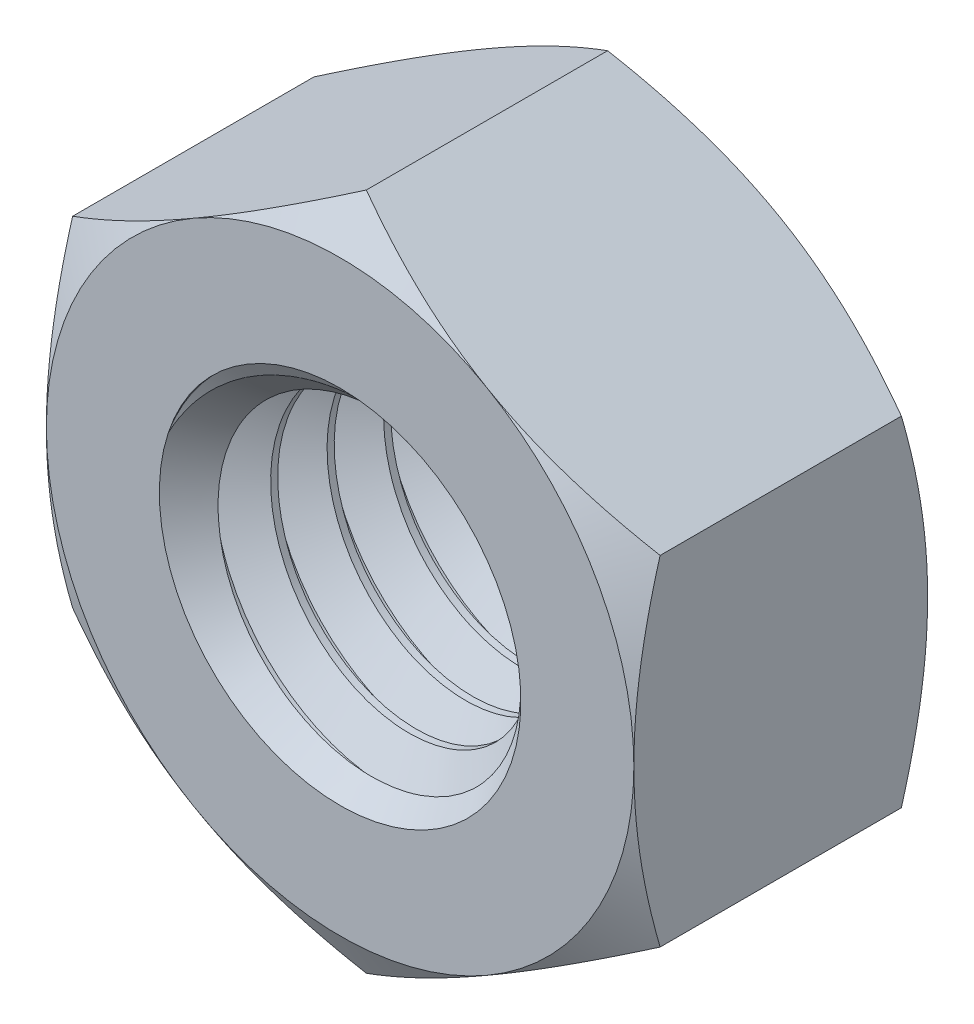
SolidWorks part; units mm, degrees
ref_plane "Front" through (0, 0, 0) normal (0, 0, 1) x (1, 0, 0)
ref_plane "Top" through (0, 0, 0) normal (0, 1, 0) x (1, 0, 0)
ref_plane "Right" through (0, 0, 0) normal (1, 0, 0) x (0, 0, -1)
sketch "Sketch1" plane through (0, 0, 0) normal (0, 0, 1) x (1, 0, 0)
  line L1 (-6.5, 3.7528) -> (-6.5, -3.7528)
  line L2 (-6.5, -3.7528) -> (0, -7.5056)
  line L3 (0, -7.5056) -> (6.5, -3.7528)
  line L4 (6.5, -3.7528) -> (6.5, 3.7528)
  line L5 (6.5, 3.7528) -> (0, 7.5056)
  line L6 (0, 7.5056) -> (-6.5, 3.7528)
  circle A0 centre (0, 0) radius 6.5 construction
  circle A1 centre (0, 0) radius 4 construction
  point P10 (0, 4)
  dimension "hex" = 13
  dimension "dia" = 8
extrude "Extrude1" add sketch "Sketch1" along normal mid plane 6.5
sketch "Sketch4" plane through (0, 0, -3.25) normal (0, 0, -1) x (-1, 0, 0)
  circle A0 centre (0, 0) radius 4 construction
  circle A1 centre (0, 0) radius 4
sketch "Sketch10" plane through (0, 0, 3.25) normal (0, 0, 1) x (1, 0, 0)
  circle A0 centre (0, 0) radius 4 construction
  circle A1 centre (0, 0) radius 4
extrude "Cut-Extrude2" cut sketch "Sketch10" against normal through all draft 45
sketch "Sketch11" plane through (0, 0, -3.25) normal (0, 0, -1) x (-1, 0, 0)
  circle A0 centre (0, 0) radius 4 construction
  circle A1 centre (0, 0) radius 4
extrude "Cut-Extrude3" cut sketch "Sketch11" against normal through all draft 45
sketch "Sketch13" plane through (0, 0, -3.25) normal (0, 0, -1) x (-1, 0, 0)
  circle A0 centre (0, 0) radius 4 construction
  circle A1 centre (0, 0) radius 4
extrude "Boss-Extrude1" add sketch "Sketch13" against normal up to vertex (6.5 mm away) separate body up to point (-6.5, 3.7528, 3.25)
curve "Helix/Spiral3" pitch 1.25 height 6.5 turns 5.2
sketch "Sketch12" plane through (0, 0, 0) normal (1, 0, 0) x (0, 0, -1)
  line L0 (4.3438, 4) -> (3.25, 4)
  line L1 (4.3438, 4) -> (3.875, 3.1881)
  line L2 (3.875, 3.1881) -> (3.7188, 3.1881)
  line L3 (3.7188, 3.1881) -> (3.25, 4)
  line L4 (3.7969, 3.1881) -> (3.7969, 4) construction
  line L5 (3.4844, 3.5941) -> (4.1094, 3.5941) construction
  dimension "D1" = 60
  dimension "D2" = 0.1562
  dimension "D3" = 0.625
sweep "Cut-Sweep1" cut profiles "Sketch12" path "Helix/Spiral3"
combine bodies "Combine1" operation type subtract main body 116 bodies to subtract 118
sketch "Sketch7" plane through (0, 0, 3.25) normal (0, 0, 1) x (1, 0, 0)
  circle A0 centre (0, 0) radius 6.5 construction
  circle A1 centre (0, 0) radius 6.5
extrude "Extrude2" cut sketch "Sketch7" against normal blind 25.4 draft 60 flip side to cut
mirror "Mirror2" about plane through (0, 0, 0) normal (0, 0, 1) of "Extrude2"
sketch "Sketch8" plane through (0, 0, 3.25) normal (0, 0, 1) x (1, 0, 0)
  line L0 (-2.8284, 2.8284) -> (0, 0) construction
  line L1 (0, -4.0599) -> (0, 4.0599) construction
  circle A1 centre (0, 0) radius 4 construction
  point P0 (-2.8284, 2.8284)
  dimension "D1" = 45
sketch "Sketch14" plane through (0, 0, 3.25) normal (0, 0, 1) x (1, 0, 0)
  line L0 (0, 0) -> (-4, 0) construction
  arc A0 (0, 4) -> (-3.8018, 1.2434) centre (0, 0) ccw construction
equation "\"D3@Helix/Spiral3\" = \"length@Extrude1\" "
equation "\"D2@Sketch12\" = \"D4@Helix/Spiral3\"*.125"
equation "\"D3@Sketch12\" = \"D4@Helix/Spiral3\"*.50"
